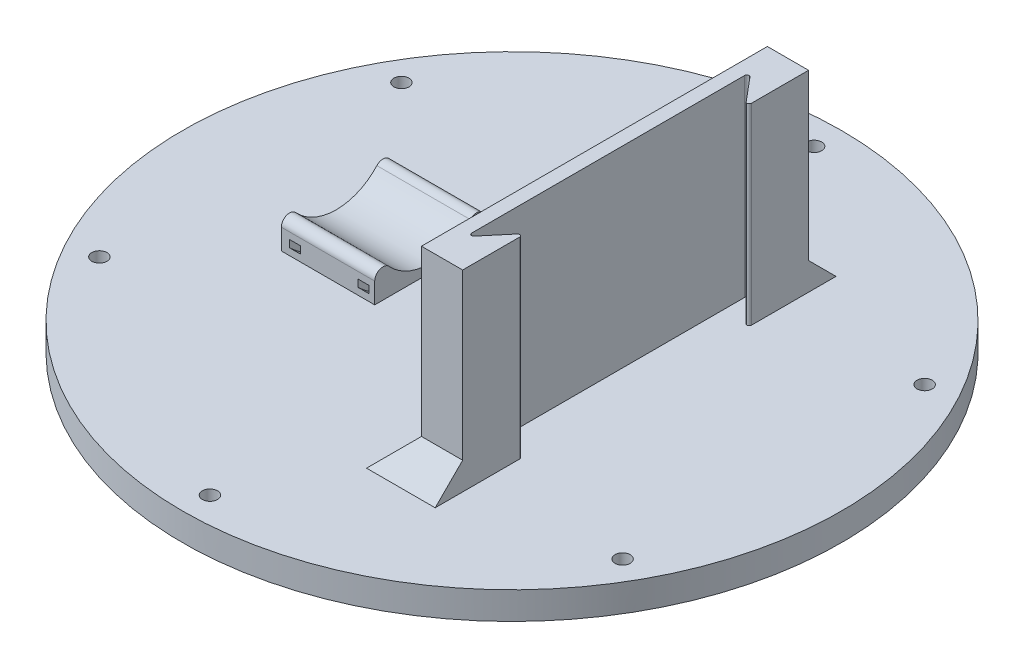
SolidWorks part; units mm, degrees
ref_plane "Front Plane" through (0, 0, 0) normal (0, 0, 1) x (1, 0, 0)
ref_plane "Top Plane" through (0, 0, 0) normal (0, 1, 0) x (1, 0, 0)
ref_plane "Right Plane" through (0, 0, 0) normal (1, 0, 0) x (0, 0, -1)
sketch "Sketch1" plane through (0, 0, 0) normal (0, 1, 0) x (1, 0, 0)
  circle A0 centre (0, 0) radius 127
  dimension "D1" = 254
  dimension "D2" = 0
extrude "Boss-Extrude1" add sketch "Sketch1" along normal blind 19.05
sketch "Sketch2" plane through (0, 19.05, 0) normal (0, 1, 0) x (1, 0, 0)
  line L0 (-16.764, 16.002) -> (-16.764, -16.002)
  line L1 (0.6783, 15.2249) -> (-16.764, 16.002)
  line L2 (0.6783, -15.2249) -> (-16.764, -16.002)
  arc A0 (0.6783, -15.2249) -> (0.6783, 15.2249) centre (0, 0) ccw
  point P5 (-16.764, 0)
  dimension "D1" = 30.48
  dimension "D2" = 32.004
  dimension "D3" = 16.764
extrude "Cut-Extrude1" cut sketch "Sketch2" against normal blind 19.05
ref_plane "Plane1" through (-38.1, 0, 0) normal (1, 0, 0) x (0, 0, -1)
sketch "Sketch3" plane through (-38.1, 0, 0) normal (1, 0, 0) x (0, 0, -1)
  line L0 (-25.4, 19.05) -> (25.4, 19.05)
  line L1 (127, 19.05) -> (-127, 19.05) construction
  line L2 (25.4, 19.05) -> (25.4, 48.26)
  line L4 (-25.4, 48.26) -> (-25.4, 19.05)
  arc A0 (-25.4, 48.26) -> (25.4, 48.26) centre (0, 48.26) ccw
  dimension "D1" = 50.8
  dimension "D2" = 29.21
extrude "Boss-Extrude2" add sketch "Sketch3" against normal blind 43.18 contours A0 L2 L0 L4
fillet "Fillet1" radius 3.81 2 edges at (-59.69, 48.26, -25.4) (-59.69, 48.26, 25.4)
sketch "Sketch7" plane through (-38.1, 0, 0) normal (1, 0, 0) x (0, 0, -1)
  circle A0 centre (0, 48.26) radius 36.3855
  circle A1 centre (0, 48.26) radius 34.0761
  arc A2 (-18.7739, 31.1515) -> (18.7739, 31.1515) centre (0, 48.26) ccw construction
extrude "Cut-Extrude4" cut sketch "Sketch7" against normal mid plane 5.08 from offset 5.08 offset against normal yes
sketch "Sketch8" plane through (-38.1, 0, -38.1) normal (1, 0, 0) x (0, 0, -1)
  circle A0 centre (-38.1, 48.26) radius 36.3855
  circle A1 centre (-38.1, 48.26) radius 34.0761
  arc A3 (-56.8739, 31.1515) -> (-19.3261, 31.1515) centre (-38.1, 48.26) ccw construction
extrude "Cut-Extrude5" cut sketch "Sketch8" against normal mid plane 5.08 from offset 36.83 offset against normal yes
sketch "Sketch4" plane through (0, 0, 0) normal (0, 1, 0) x (1, 0, 0)
  circle A0 centre (0, 0) radius 127
  circle A1 centre (0, 0) radius 152.4
  dimension "D1" = 254
  dimension "D2" = 304.8
extrude "Boss-Extrude3" add sketch "Sketch4" along normal blind 190.5
sketch "Sketch5" plane through (0, 190.5, -228.6) normal (0, -1, 0) x (1, 0, 0)
  line L0 (0, 0) -> (0, 149.8525) construction
  line L1 (-25.4, 351.7376) -> (-25.4, 378.8684)
  line L2 (25.4, 351.7376) -> (25.4, 378.8684)
  line L3 (93.9403, 312.1659) -> (117.4363, 325.7313)
  line L4 (119.3403, 268.1718) -> (142.8363, 281.7372)
  line L5 (119.3403, 189.0282) -> (142.8363, 175.4628)
  line L6 (93.9403, 145.0341) -> (117.4363, 131.4687)
  line L7 (25.4, 105.4624) -> (25.4, 78.3316)
  line L8 (-25.4, 105.4624) -> (-25.4, 78.3316)
  line L9 (-93.9403, 145.0341) -> (-117.4363, 131.4687)
  line L10 (-119.3403, 189.0282) -> (-142.8363, 175.4628)
  line L11 (-119.3403, 268.1718) -> (-142.8363, 281.7372)
  line L12 (-93.9403, 312.1659) -> (-117.4363, 325.7313)
  arc A0 (-25.4, 351.7376) -> (-93.9403, 312.1659) centre (0, 228.6) ccw
  arc A1 (25.4, 378.8684) -> (-25.4, 378.8684) centre (0, 228.6) ccw
  arc A2 (142.8363, 281.7372) -> (117.4363, 325.7313) centre (0, 228.6) ccw
  arc A3 (117.4363, 131.4687) -> (142.8363, 175.4628) centre (0, 228.6) ccw
  arc A4 (-25.4, 78.3316) -> (25.4, 78.3316) centre (0, 228.6) ccw
  arc A5 (-142.8363, 175.4628) -> (-117.4363, 131.4687) centre (0, 228.6) ccw
  arc A6 (-117.4363, 325.7313) -> (-142.8363, 281.7372) centre (0, 228.6) ccw
  arc A7 (-119.3403, 268.1718) -> (-119.3403, 189.0282) centre (0, 228.6) ccw
  arc A8 (93.9403, 312.1659) -> (25.4, 351.7376) centre (0, 228.6) ccw
  arc A9 (119.3403, 189.0282) -> (119.3403, 268.1718) centre (0, 228.6) ccw
  arc A10 (25.4, 105.4624) -> (93.9403, 145.0341) centre (0, 228.6) ccw
  arc A11 (-93.9403, 145.0341) -> (-25.4, 105.4624) centre (0, 228.6) ccw
  point P32 (0, 228.6)
  dimension "D1" = 251.46
  dimension "D2" = 304.8
  dimension "D3" = 50.8
  dimension "D4" = 6
extrude "Cut-Extrude2" cut sketch "Sketch5" along normal blind 12.7
sketch "Sketch6" plane through (0, 190.5, 0) normal (0, 1, 0) x (1, 0, 0)
  circle A0 centre (0, 0) radius 139.7 construction
  circle A1 centre (0, 139.7) radius 3.5116
  circle A2 centre (120.9837, 69.85) radius 3.5116
  circle A3 centre (120.9837, -69.85) radius 3.5116
  circle A4 centre (0, -139.7) radius 3.5116
  circle A5 centre (-120.9837, -69.85) radius 3.5116
  circle A6 centre (-120.9837, 69.85) radius 3.5116
  point P3 (0, 139.7)
  point P6 (120.9837, 69.85)
  point P7 (120.9837, -69.85)
  point P8 (0, -139.7)
  point P9 (-120.9837, -69.85)
  point P10 (-120.9837, 69.85)
  point P11 (0, 0)
  dimension "D1" = 279.4
  dimension "D3" = 7.0231
  dimension "D2" = 6
extrude "Cut-Extrude6" cut sketch "Sketch6" against normal blind 171.45 from surface starting at face at (-119.9667, 177.8, 69.2628)
sketch "Sketch9" plane through (0, 19.05, 0) normal (0, 1, 0) x (1, 0, 0)
  line L0 (38.1, 121.1503) -> (38.1, -121.1503)
  line L1 (57.15, 113.4146) -> (57.15, -113.4146)
  arc A1 (25.4, -124.4341) -> (95.0631, -84.2141) centre (0, 0) ccw construction
  circle A2 centre (0, 0) radius 127 construction
  arc A3 (38.1, -121.1503) -> (57.15, -113.4146) centre (0, 0) ccw
  arc A4 (57.15, 113.4146) -> (38.1, 121.1503) centre (0, 0) ccw
  dimension "D1" = 19.05
  dimension "D2" = 38.1
extrude "Boss-Extrude4" add sketch "Sketch9" along normal blind 88.9
sketch "Sketch10" plane through (0, 107.95, 0) normal (0, 1, 0) x (1, 0, 0)
  line L0 (57.15, -50.8) -> (57.15, 50.8)
  line L2 (57.15, -113.4146) -> (57.15, 113.4146) construction
  line L3 (44.45, -65.9353) -> (44.45, 65.9353)
  line L4 (44.45, 65.9353) -> (57.15, 50.8)
  line L5 (44.45, -65.9353) -> (57.15, -50.8)
  point P3 (57.15, 0)
  point P8 (44.45, 0)
  dimension "D1" = 12.7
  dimension "D2" = 40
  dimension "D3" = 40
  dimension "D4" = 101.6
extrude "Cut-Extrude8" cut sketch "Sketch10" against normal up to surface (88.9 mm away) contours L4 L0 L5 L3 up to face at (-4.4024, 19.05, 0)
fillet "Fillet2" radius 1.016 4 edges at (57.15, 63.5, -50.8) (44.45, 63.5, -65.9353) (44.45, 63.5, 65.9353) (57.15, 63.5, 50.8)
sketch "Sketch11" plane through (0, 0, 0) normal (0, -1, 0) x (1, 0, 0)
  line L0 (-16.764, 16.002) -> (-16.764, -16.002)
  line L1 (-16.764, -16.002) -> (0.6783, -15.2249)
  line L2 (-16.764, 16.002) -> (0.6783, 15.2249) construction
  line L3 (0.6783, 15.2249) -> (-16.764, 16.002)
  line L4 (-29.464, 29.2804) -> (-29.464, -29.2804)
  line L5 (-29.464, -29.2804) -> (1.2436, -27.9123)
  line L6 (1.2436, 27.9123) -> (-29.464, 29.2804)
  arc A0 (0.6783, -15.2249) -> (0.6783, 15.2249) centre (0, 0) ccw
  arc A1 (1.2436, -27.9123) -> (1.2436, 27.9123) centre (0, 0) ccw
  arc A2 (0.6783, -15.2249) -> (0.6783, 15.2249) centre (0, 0) ccw construction
  dimension "D1" = 12.7
  dimension "D2" = 12.7
extrude "Cut-Extrude9" cut sketch "Sketch11" against normal blind 16.51
sketch "Sketch14" plane through (0, 190.5, 0) normal (0, 1, 0) x (1, 0, 0)
  circle A0 centre (0, 0) radius 152.4
  circle A1 centre (0, 0) radius 127
extrude "Cut-Extrude12" cut sketch "Sketch14" against normal up to surface (171.45 mm away) up to face at (-4.4024, 19.05, 0)
sketch "Sketch15" plane through (0, 0, 0) normal (0, -1, 0) x (1, 0, 0)
  circle A0 centre (0, 0) radius 152.4
extrude "Cut-Extrude13" cut sketch "Sketch15" against normal blind 6.35
sketch "Sketch17" plane through (0, 107.95, 0) normal (0, 1, 0) x (1, 0, 0)
  line L0 (0, 0) -> (83.2893, 0) construction
  line L1 (38.1, 121.1503) -> (38.1, 79.9856)
  line L2 (38.1, 121.1503) -> (38.1, -121.1503) construction
  line L3 (38.1, 79.9856) -> (57.15, 79.9856)
  line L4 (57.15, 53.5914) -> (57.15, 113.4146) construction
  line L5 (57.15, 79.9856) -> (57.15, 121.1503)
  line L6 (57.15, 121.1503) -> (38.1, 121.1503)
  line L7 (38.1, -79.9856) -> (57.15, -79.9856)
  line L8 (57.15, -79.9856) -> (57.15, -121.1503)
  line L9 (38.1, -121.1503) -> (38.1, -79.9856)
  line L10 (57.15, -121.1503) -> (38.1, -121.1503)
extrude "Cut-Extrude15" cut sketch "Sketch17" against normal up to surface (88.9 mm away) up to face at (49.7678, 19.05, 0)
chamfer "Chamfer2" distance 12.7 angle 45 3 edges at (47.625, 19.05, -79.9856) (38.1, 19.05, 0) (47.625, 19.05, 79.9856)
equation "\"bottom_d\"=10"
equation "\"D1@Sketch1\"=\"bottom_d\""
equation "\"D1@Sketch4\"=\"bottom_d\""
equation "\"D2@Sketch4\"=\"bottom_d\"+2"
